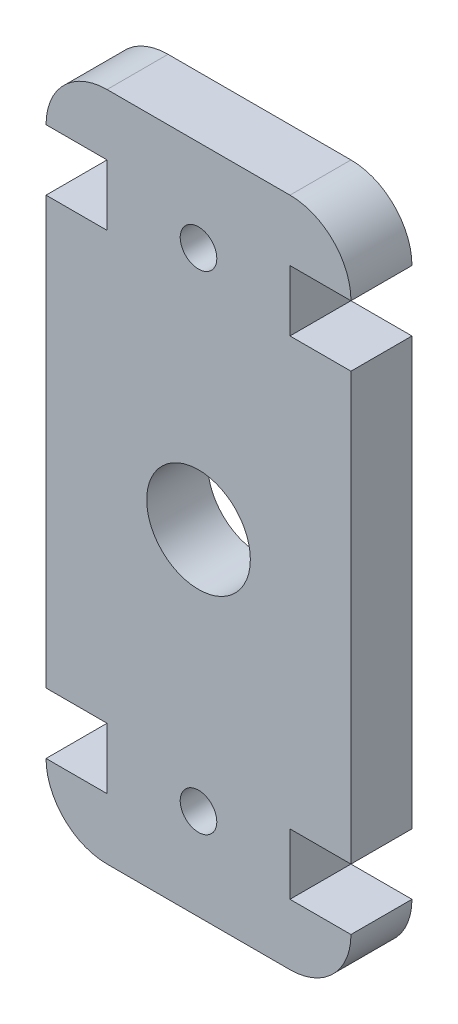
SolidWorks part; units mm, degrees
ref_plane "Plan de face" through (0, 0, 0) normal (0, 0, 1) x (1, 0, 0)
ref_plane "Plan de dessus" through (0, 0, 0) normal (0, 1, 0) x (1, 0, 0)
ref_plane "Plan de droite" through (0, 0, 0) normal (1, 0, 0) x (0, 0, -1)
sketch "Esquisse1" plane through (0, 0, 0) normal (0, 0, 1) x (1, 0, 0)
  line L0 (-12.5, 0) -> (12.5, 0)
  line L1 (12.5, 0) -> (12.5, 5)
  line L2 (12.5, 5) -> (7.5, 5)
  line L3 (7.5, 5) -> (7.5, 10)
  line L4 (7.5, 10) -> (12.5, 10)
  line L5 (12.5, 10) -> (12.5, 45)
  line L6 (12.5, 45) -> (7.5, 45)
  line L7 (7.5, 45) -> (7.5, 50)
  line L8 (7.5, 50) -> (12.5, 50)
  line L9 (12.5, 50) -> (12.5, 55)
  line L10 (12.5, 55) -> (-12.5, 55)
  line L11 (-12.5, 55) -> (-12.5, 50)
  line L12 (-12.5, 50) -> (-7.5, 50)
  line L13 (-7.5, 50) -> (-7.5, 45)
  line L14 (-7.5, 45) -> (-12.5, 45)
  line L15 (-12.5, 45) -> (-12.5, 10)
  line L16 (-12.5, 10) -> (-7.5, 10)
  line L17 (-7.5, 10) -> (-7.5, 5)
  line L18 (-7.5, 5) -> (-12.5, 5)
  line L19 (-12.5, 5) -> (-12.5, 0)
  line L20 (0, 0) -> (0, 55) construction
  line L21 (-7.5, 7.5) -> (7.5, 7.5) construction
  line L22 (7.5, 47.5) -> (-7.5, 47.5) construction
  line L23 (-12.5, 27.5) -> (12.5, 27.5) construction
  circle A0 centre (0, 47.5) radius 1.5
  circle A1 centre (0, 7.5) radius 1.5
  circle A2 centre (0, 27.5) radius 4.25
  circle A3 centre (-20, 27.5) radius 1.6 construction
  circle A4 centre (20, 27.5) radius 1.6 construction
  dimension "D6" = 3
  dimension "D7" = 3
  dimension "D8" = 8.5
  dimension "D10" = 3.2
  dimension "D1" = 5
  dimension "D2" = 5
  dimension "D3" = 25
  dimension "D4" = 5
  dimension "D5" = 40
  dimension "D11" = 20
extrude "Boss.-Extru.1" add sketch "Esquisse1" along normal blind 5
fillet "Congé1" radius 5 4 edges at (12.5, 55, 2.5) (12.5, 0, 2.5) (-12.5, 0, 2.5) (-12.5, 55, 2.5)
